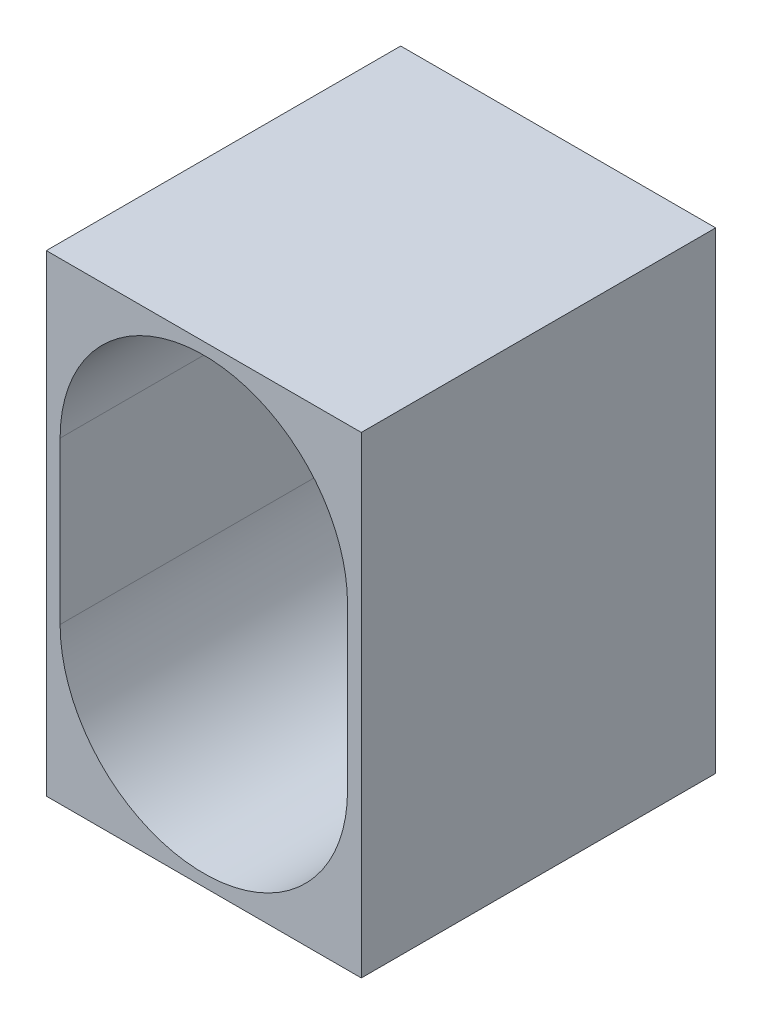
SolidWorks part; units mm, degrees
ref_plane "Front Plane" through (0, 0, 0) normal (0, 0, 1) x (1, 0, 0)
ref_plane "Top Plane" through (0, 0, 0) normal (0, 1, 0) x (1, 0, 0)
ref_plane "Right Plane" through (0, 0, 0) normal (1, 0, 0) x (0, 0, -1)
sketch "Sketch4" plane through (0, 0, 0) normal (0, 0, 1) x (1, 0, 0)
  line L1 (-25.2849, 20.5607) -> (14.7151, 20.5607)
  line L2 (-25.2849, 20.5607) -> (-25.2849, -39.4393)
  line L3 (-25.2849, -39.4393) -> (14.7151, -39.4393)
  line L4 (14.7151, 20.5607) -> (14.7151, -39.4393)
  dimension "D1" = 40
  dimension "D2" = 60
extrude "Boss-Extrude2" add sketch "Sketch4" along normal blind 45
sketch "Sketch5" plane through (0, 0, 45) normal (0, 0, 1) x (1, 0, 0)
  line L0 (-5.2849, -19.6893) -> (-5.2849, 0.8107) construction
  line L1 (-18.5349, -19.6893) -> (-18.5349, 0.8107) construction
  line L2 (7.9651, -19.6893) -> (7.9651, 0.8107) construction
  line L3 (-25.2849, -39.4393) -> (14.7151, -39.4393) construction
  line L4 (-25.2849, 20.5607) -> (-25.2849, -39.4393) construction
  line L5 (-23.5349, -19.6893) -> (-23.5349, 0.8107)
  line L6 (12.9651, -19.6893) -> (12.9651, 0.8107)
  arc A0 (-18.5349, -19.6893) -> (7.9651, -19.6893) centre (-5.2849, -19.6893) ccw construction
  arc A1 (7.9651, 0.8107) -> (-18.5349, 0.8107) centre (-5.2849, 0.8107) ccw construction
  arc A2 (12.9651, 0.8107) -> (-23.5349, 0.8107) centre (-5.2849, 0.8107) ccw
  arc A3 (-23.5349, -19.6893) -> (12.9651, -19.6893) centre (-5.2849, -19.6893) ccw
  point P2 (-5.2849, -9.4393)
  dimension "D3" = 5
  dimension "D1" = 30
  dimension "D2" = 20
extrude "Cut-Extrude1" cut sketch "Sketch5" against normal blind 42.5
